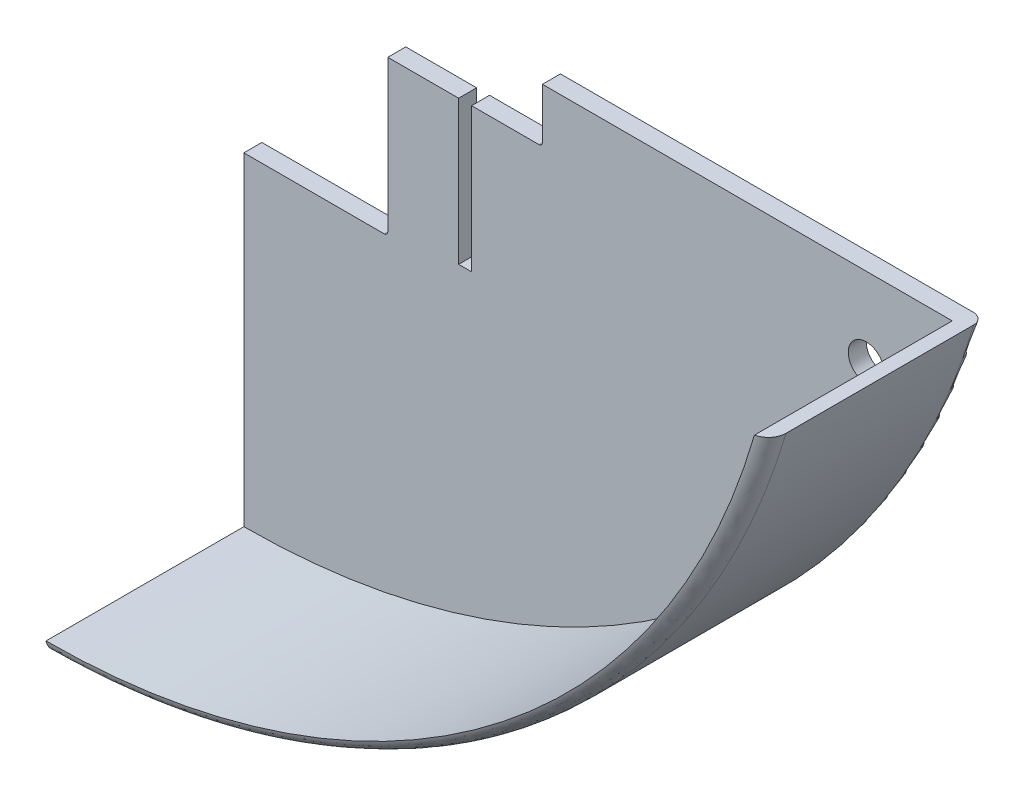
SolidWorks part; units mm, degrees
ref_plane "Alzado" through (0, 0, 0) normal (0, 0, 1) x (1, 0, 0)
ref_plane "Planta" through (0, 0, 0) normal (0, 1, 0) x (1, 0, 0)
ref_plane "Vista lateral" through (0, 0, 0) normal (1, 0, 0) x (0, 0, -1)
sketch "Sketch2" plane through (0, 0, 0) normal (0, 0, 1) x (1, 0, 0)
  line L0 (172.6869, -140.2289) -> (172.6869, -70.2289)
  line L1 (255.6869, -7.2289) -> (345.6869, -7.2289) construction
  line L3 (172.6869, -144.2289) -> (172.6869, -140.2289)
  line L4 (255.6869, 7.7711) -> (373.5501, 7.7711)
  line L5 (345.6869, -7.2289) -> (345.6869, -14.2289) construction
  line L8 (172.6869, -70.2289) -> (172.6869, -50.2289)
  line L9 (212.6869, -50.2289) -> (212.6869, -7.2289)
  line L10 (212.6869, -7.2289) -> (232.3869, -7.2289)
  line L11 (255.6869, -7.2289) -> (255.6869, 7.7711)
  line L13 (172.6869, -50.2289) -> (212.6869, -50.2289)
  line L17 (235.9869, -7.2289) -> (255.6869, -7.2289)
  line L18 (232.3869, -7.2289) -> (232.3869, -47.2289)
  line L19 (232.3869, -47.2289) -> (235.9869, -47.2289)
  line L20 (235.9869, -7.2289) -> (235.9869, -47.2289)
  arc A0 (172.6869, -140.2289) -> (369.6031, 7.7711) centre (172.6869, 64.7711) ccw
  arc A1 (172.6869, -144.2289) -> (373.5501, 7.7711) centre (170.4126, 67.4937) ccw
  circle A2 centre (345.6869, -14.2289) radius 5
  dimension "D6" = 205
  dimension "D3" = 7
  dimension "D4" = 10
  dimension "D1" = 70
  dimension "D2" = 90
  dimension "D5" = 20
  dimension "D9" = 4
  dimension "D10" = 43
  dimension "D13" = 3.6
extrude "Boss-Extrude1" add sketch "Sketch2" along normal blind 60 contours L0 A0 L11 L17 L20 L19 L18 L10 L9 | L3 A1 A0 region at (297.3669, -101.1175, 0) region at (259.9851, -60.1666, 0)
sketch "Sketch3" plane through (0, 0, 60) normal (0, 0, 1) x (1, 0, 0)
  line L12 (172.6869, -140.2289) -> (172.6869, 7.7711)
  line L13 (369.6031, 7.7711) -> (172.6869, 7.7711)
  arc A0 (172.6869, -140.2289) -> (369.6031, 7.7711) centre (172.6869, 64.7711) ccw
extrude "Cut-Extrude1" cut sketch "Sketch3" against normal blind 55
sketch "Sketch4" plane through (0, 0, 0) normal (0, 0, -1) x (-1, 0, 0)
  line L8 (-172.6869, -140.2289) -> (-172.6869, -70.2289) construction
  line L9 (-172.6869, -125.2289) -> (-217.6869, -125.2289)
  line L10 (-172.6869, -125.2289) -> (-172.6869, -115.2289)
  line L11 (-172.6869, -65.2289) -> (-217.6869, -65.2289)
  line L12 (-217.6869, -125.2289) -> (-217.6869, -65.2289)
  line L13 (-172.6869, -75.2289) -> (-172.6869, -65.2289)
  line L14 (-172.6869, -115.2289) -> (-207.6869, -115.2289)
  line L16 (-172.6869, -75.2289) -> (-207.6869, -75.2289)
  line L17 (-207.6869, -115.2289) -> (-207.6869, -75.2289)
  dimension "D1" = 60
  dimension "D2" = 15
  dimension "D5" = 10
  dimension "D6" = 10
  dimension "D7" = 10
  dimension "D8" = 45
extrude "Cut-Extrude2" cut sketch "Sketch4" against normal blind 3.5
fillet "Fillet1" radius 3 1 edges at (298.18, -101.3469, 0)
fillet "Fillet2" radius 1 2 edges at (255.6869, -7.2289, 2.5) (212.6869, -50.2289, 2.5)
fillet "Fillet5" radius 5 1 edges at (298.18, -101.3469, 60)
sketch "Sketch5" plane through (0, 0, 0) normal (0, 0, -1) x (-1, 0, 0)
  line L0 (-369.6031, 7.7711) -> (-255.6869, 7.7711) construction
  line L5 (-235.9869, -7.2289) -> (-235.9869, -47.2289) construction
  line L6 (-270.9869, -67.5494) -> (-291.5818, -67.5494) construction
  line L7 (-270.9869, -67.5494) -> (-302.1638, -49.5494)
  line L8 (-270.9869, -67.5494) -> (-260.9869, -50.2289)
  line L9 (-260.9869, -50.2289) -> (-292.1638, -32.2289)
  line L10 (-292.1638, -32.2289) -> (-302.1638, -49.5494)
  line L11 (-190.6869, -85.2289) -> (-172.6869, -85.2289)
  line L12 (-172.6869, -85.2289) -> (-172.6869, -105.2289)
  line L13 (-172.6869, -105.2289) -> (-190.6869, -105.2289)
  line L14 (-190.6869, -105.2289) -> (-190.6869, -85.2289)
  line L15 (-172.6869, -115.2289) -> (-172.6869, -75.2289) construction
  line L16 (-207.6869, -75.2289) -> (-172.6869, -75.2289) construction
  point P0 (-260.9869, -50.2289)
  point P1 (-292.1638, -32.2289)
  dimension "D1" = 40
  dimension "D2" = 25
  dimension "D3" = 30
  dimension "D4" = 36
  dimension "D5" = 20
  dimension "D6" = 20
  dimension "D7" = 10
  dimension "D8" = 18
extrude "Cut-Extrude3" cut sketch "Sketch5" against normal blind 3.5
fillet "Fillet6" radius 7 6 edges at (292.1638, -32.2289, 1.75) (302.1638, -49.5494, 1.75) (260.9869, -50.2289, 1.75) (270.9869, -67.5494, 1.75) (190.6869, -105.2289, 1.75) (190.6869, -85.2289, 1.75)
fillet "Fillet7" radius 8 2 edges at (217.6869, -125.2289, 1.75) (217.6869, -65.2289, 1.75)
fillet "Fillet8" radius 5 2 edges at (207.6869, -115.2289, 1.75) (207.6869, -75.2289, 1.75)
